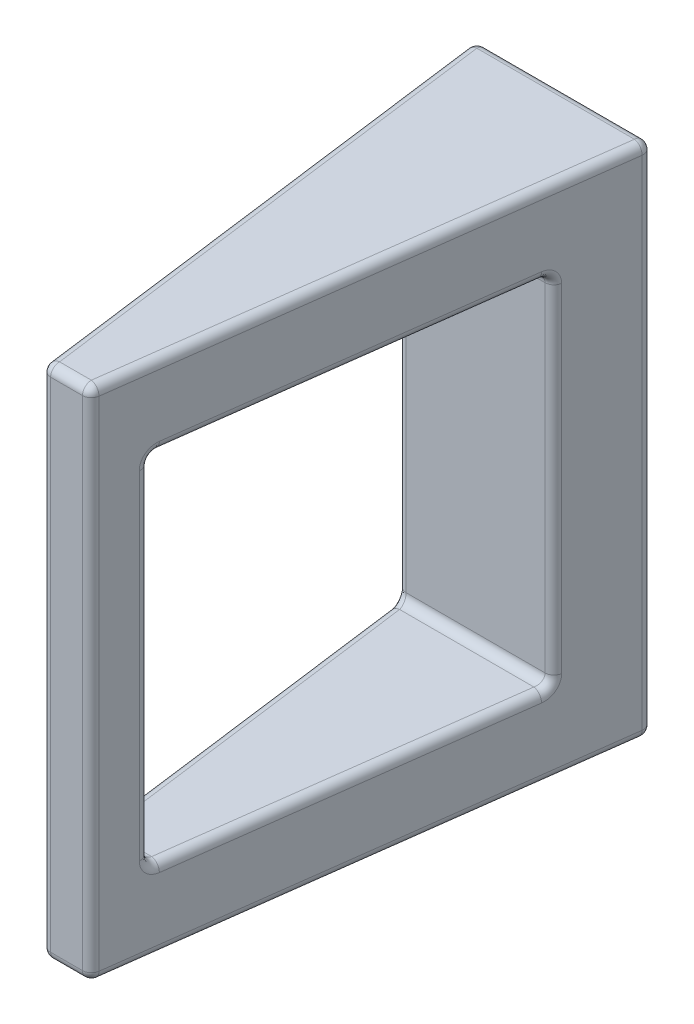
SolidWorks part; units mm, degrees
ref_plane "Front Plane" through (0, 0, 0) normal (1, 0, 0) x (0, 1, 0)
ref_plane "Top Plane" through (0, 0, 0) normal (0, 0, 1) x (0, 1, 0)
ref_plane "Right Plane" through (0, 0, 0) normal (0, 1, 0) x (-1, 0, 0)
sketch "A-Frame Profile" plane through (0, 0, 0) normal (0, 1, 0) x (-1, 0, 0)
  line L0 (-31.75, 0) -> (31.75, 0)
  line L1 (31.75, 0) -> (8.4667, 177.8)
  line L2 (8.4667, 177.8) -> (-8.4667, 177.8)
  line L3 (-8.4667, 177.8) -> (-31.75, 0)
extrude "A-Frame Body" add sketch "A-Frame Profile" along normal blind 92.075 and the other way blind 92.075
sketch "Window Sketch" plane through (0, 0, 0) normal (1, 0, 0) x (0, 1, 0)
  line L0 (-63.5, 31.75) -> (63.5, 31.75)
  line L1 (63.5, 31.75) -> (63.5, 158.75)
  line L2 (63.5, 158.75) -> (-63.5, 158.75)
  line L3 (-63.5, 158.75) -> (-63.5, 31.75)
extrude "Window Cutout" cut sketch "Window Sketch" against normal through all and the other way through all
sketch "Mounting Holes Sketch" plane through (0, 0, 0) normal (0, 0, 1) x (0, 1, 0)
  circle A0 centre (-31.75, 0) radius 3.9688
  circle A1 centre (31.75, 0) radius 3.9688
extrude "Mounting Holes" cut sketch "Mounting Holes Sketch" along normal blind 12.7
fillet "External Fillets" radius 3.175 28 edges at (3.9688, 31.75, 12.7) (3.9688, 31.75, 0) (3.9688, -31.75, 0) (3.9688, -31.75, 12.7) (0, -63.5, 31.75) (0, 63.5, 31.75) (0, 63.5, 158.75) (0, -63.5, 158.75) (27.5923, 0, 31.75) (19.2768, 63.5, 95.25) (10.9613, 0, 158.75) (19.2768, -63.5, 95.25) (20.1083, 92.075, 88.9) (0, 92.075, 0) (-20.1083, 92.075, 88.9) (0, 92.075, 177.8) (20.1083, -92.075, 88.9) (0, -92.075, 0) (-20.1083, -92.075, 88.9) (0, -92.075, 177.8) (31.75, 0, 0) (-31.75, 0, 0) (-8.4667, 0, 177.8) (8.4667, 0, 177.8) (-27.5923, 0, 31.75) (-19.2768, 63.5, 95.25) (-10.9613, 0, 158.75) (-19.2768, -63.5, 95.25) tangent propagation no
